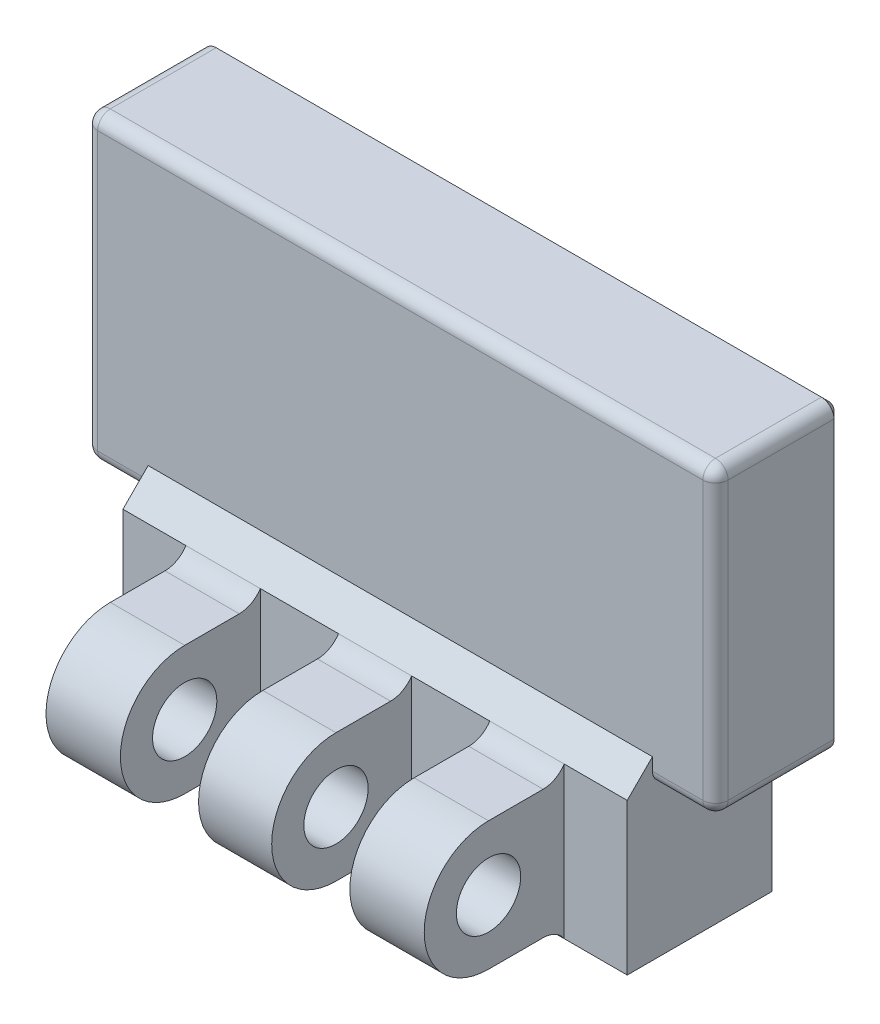
SolidWorks part; units mm, degrees
note: The reader was unsure of these and kept them because the rebuilt part matched: shared geometry of "Sketch3<2>".
ref_plane "Front Plane" through (0, 0, 0) normal (0, 0, 1) x (1, 0, 0)
ref_plane "Top Plane" through (0, 0, 0) normal (0, 1, 0) x (1, 0, 0)
ref_plane "Right Plane" through (0, 0, 0) normal (1, 0, 0) x (0, 0, -1)
sketch "Sketch1" plane through (0, 0, 0) normal (0, 0, 1) x (1, 0, 0)
  line L0 (0, 0) -> (0, 31.117) construction
  line L4 (-20, -6) -> (20, -6)
  line L5 (-20, -6) -> (-20, 6)
  line L6 (-20, 6) -> (20, 6)
  line L7 (20, -6) -> (20, 6)
  line L8 (-20, -6) -> (20, 6) construction
  line L9 (-20, 6) -> (20, -6) construction
  circle A0 centre (11, 0) radius 4.05
  circle A1 centre (-11, 0) radius 4.05
  dimension "D1" = 8.1
  dimension "D3" = 12
  dimension "D2" = 22
  dimension "D4" = 40
extrude "Boss-Extrude1" add sketch "Sketch1" along normal mid plane 12
sketch "Sketch3" plane through (0, 0, 0) normal (1, 0, 0) x (0, 0, -1)
  line L0 (-12, -5.1) -> (-6, -5.1)
  line L2 (-12, 5.1) -> (-6, 5.1)
  line L3 (-6, 5.1) -> (-6, -5.1)
  line L4 (-6, -6) -> (-6, 6) construction
  circle A1 centre (-12, 0) radius 2.55
  arc A2 (-12, 5.1) -> (-12, -5.1) centre (-12, 0) ccw
  dimension "D1" = 5.1
  dimension "D2" = 5.1
  dimension "D3" = 12
extrude "Boss-Extrude2" add sketch "Sketch3" along normal mid plane 30
extrude "Cut-Extrude1" cut sketch "Sketch3<2>" against normal blind 6.2 from offset 2.9 offset against normal yes
sketch "Sketch3<2>" plane through (0, 0, 0) normal (1, 0, 0) x (0, 0, -1) same geometry as "Sketch3"
mirror "Mirror1" about plane through (0, 0, 0) normal (1, 0, 0) of "Cut-Extrude1"
sketch "Sketch5" plane through (0, 0, 6) normal (0, 0, 1) x (1, 0, 0)
  circle A0 centre (-11, 0) radius 4.05
  arc A1 (-9.1, -3.5767) -> (-9.1, 3.5767) centre (-11, 0) ccw construction
  circle A2 centre (11, 0) radius 4.05
  arc A3 (9.1, 3.5767) -> (9.1, -3.5767) centre (11, 0) ccw construction
extrude "Boss-Extrude3" add sketch "Sketch5" against normal blind 3
sketch "Sketch6" plane through (0, 0, -6) normal (0, 0, -1) x (-1, 0, 0)
  line L0 (-20, 6) -> (20, 6) construction
  line L7 (-25, 6) -> (25, 6)
  line L8 (-25, 6) -> (-25, 30)
  line L9 (-25, 30) -> (25, 30)
  line L10 (25, 6) -> (25, 30)
  point P5 (0, 30)
  point P6 (-21.133, 6)
  point P7 (0, 0)
  point P8 (-26.7891, 6)
  dimension "D2" = 50
  dimension "D1" = 24
extrude "Boss-Extrude4" add sketch "Sketch6" against normal blind 10
sketch "Sketch8" plane through (0, 0, -6) normal (0, 0, -1) x (-1, 0, 0)
  line L1 (-23, 6) -> (23, 6)
  line L2 (-23, 6) -> (-23, 27)
  line L3 (-23, 27) -> (23, 27)
  line L4 (23, 6) -> (23, 27)
  line L5 (-25, 6) -> (-20, 6) construction
  line L6 (20, -6) -> (-20, -6) construction
  line L7 (-5.5, 6) -> (5.5, 6)
  line L8 (-5.5, 6) -> (-5.5, -6)
  line L9 (-5.5, -6) -> (5.5, -6)
  line L10 (5.5, 6) -> (5.5, -6)
  point P7 (0, 6)
  point P14 (0, -6)
  line M11 (-20, -6) -> (20, -6)
  line M13 (20, 6) -> (25, 6)
  line M17 (-25, 6) -> (-20, 6)
  dimension "D1" = 46
  dimension "D2" = 21
  dimension "D3" = 11
extrude "Cut-Extrude2" cut sketch "Sketch8" against normal blind 8 contours L10 L1 L8 M11 | L4 L3 L2 L1 M13 M17
chamfer "Chamfer1" distance 2 angle 45 1 edges at (0, 6, 4)
fillet "Fillet1" radius 1 3 edges at (-25, 18, 4) (25, 18, 4) (0, 30, 4)
fillet "Fillet2" radius 1 10 edges at (-22, 6, 4) (-24.7071, 6, 3.7071) (22, 6, 4) (24.7071, 6, 3.7071) (-24.7071, 29.7071, 3.7071) (24.7071, 29.7071, 3.7071) (-25, 6, -1.5) (25, 6, -1.5) (-25, 30, -1.5) (25, 30, -1.5)
chamfer "Chamfer2" distance 0.6 angle 45 9 edges at (-23.5, 6, -6) (23.5, 6, -6) (-25, 18, -6) (0, 30, -6) (25, 18, -6) (24.7071, 29.7071, -6) (-24.7071, 29.7071, -6) (24.7071, 6.2929, -6) (-24.7071, 6.2929, -6)
chamfer "Chamfer3" distance 0.5 angle 45 10 edges at (12.75, -6, -6) (15.05, 0, -6) (-5.5, 0, -6) (-12.75, 6, -6) (12.75, 6, -6) (5.5, 0, -6) (-15.05, 0, -6) (-12.75, -6, -6) (-20, 0, -6) (20, 0, -6)
fillet "Fillet3" radius 2 6 edges at (-12.05, -5.1, 6) (0, -5.1, 6) (12.05, -5.1, 6) (-12.05, 5.1, 6) (0, 5.1, 6) (12.05, 5.1, 6)
